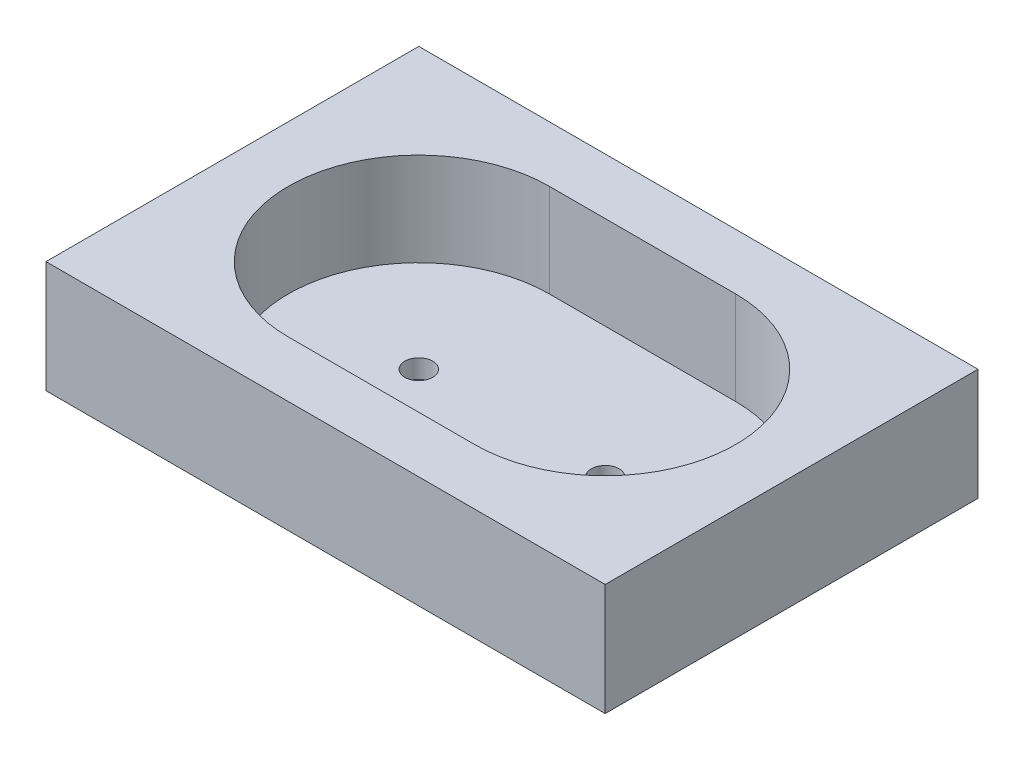
SolidWorks part; units mm, degrees
ref_plane "Front Plane" through (0, 0, 0) normal (0, 0, 1) x (1, 0, 0)
ref_plane "Top Plane" through (0, 0, 0) normal (0, 1, 0) x (1, 0, 0)
ref_plane "Right Plane" through (0, 0, 0) normal (1, 0, 0) x (0, 0, -1)
sketch "Sketch1" plane through (0, 0, 0) normal (0, 1, 0) x (1, 0, 0)
  line L0 (-20, 0) -> (0, 0) construction
  line L1 (-40, 20) -> (20, 20)
  line L2 (-40, 20) -> (-40, -20)
  line L3 (-40, -20) -> (20, -20)
  line L4 (20, 20) -> (20, -20)
  line L5 (-20, 14) -> (0, 14)
  line L6 (-20, -14) -> (0, -14)
  circle A0 centre (0, 0) radius 10 construction
  circle A1 centre (-20, 0) radius 10 construction
  arc A2 (0, -14) -> (0, 14) centre (0, 0) ccw
  circle A4 centre (0, 0) radius 1.5
  arc A5 (-20, 14) -> (-20, -14) centre (-20, 0) ccw
  circle A6 centre (-20, 0) radius 1.5
  point P9 (14, 0)
  point P10 (20, 0)
  point P15 (-34, 0)
  dimension "D1" = 20
  dimension "D2" = 4
  dimension "D6" = 6
  dimension "D7" = 3
  dimension "D8" = 3
  dimension "D3" = 6
  dimension "D4" = 6
  dimension "D5" = 6
extrude "Boss-Extrude1" add sketch "Sketch1" along normal blind 10 contours L4 L1 L2 L3 A5 L5 A2 L6 region at (-10, 0, -19.2789)
extrude "Boss-Extrude2" add sketch "Sketch1<3>" against normal blind 2 contours L4 L1 L2 L3 A5 L5 A2 L6 | L5 A5 L6 A2 A6 A4 region at (-10, 0, -19.2789) region at (-10, 0, 0)
sketch "Sketch1<3>" plane through (0, 0, 0) normal (0, 1, 0) x (1, 0, 0) same geometry as "Sketch1"
